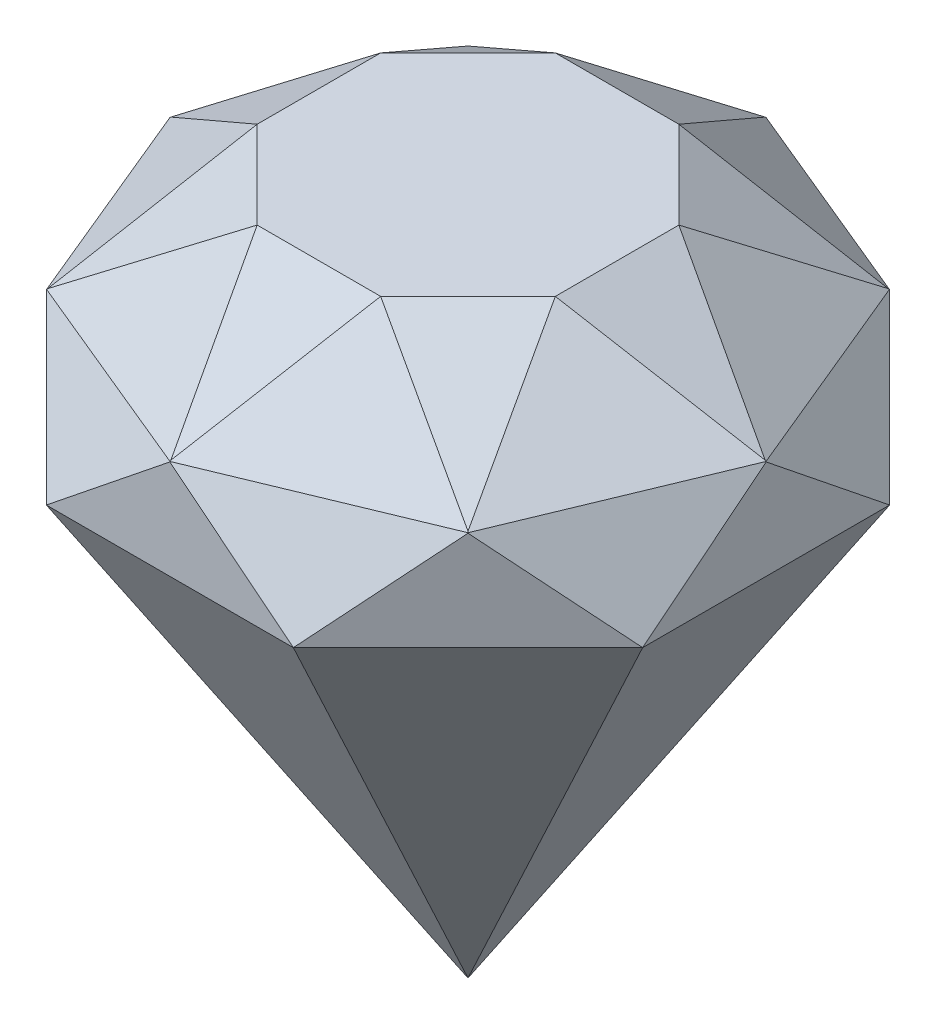
SolidWorks part; units mm, degrees
ref_plane "Front Plane" through (0, 0, 0) normal (0, 0, 1) x (1, 0, 0)
ref_plane "Top Plane" through (0, 0, 0) normal (0, 1, 0) x (1, 0, 0)
ref_plane "Right Plane" through (0, 0, 0) normal (1, 0, 0) x (0, 0, -1)
sketch "Sketch1" plane through (0, 0, 0) normal (0, 1, 0) x (1, 0, 0)
  line L0 (0, 0) -> (-12.4264, 30)
  line L1 (0, 0) -> (12.4264, 30)
  line L2 (12.4264, 30) -> (-12.4264, 30)
  line L3 (0, 0) -> (0, 30) construction
  dimension "D1" = 45
  dimension "D2" = 30
extrude "Boss-Extrude1" add sketch "Sketch1" along normal blind 70
sketch "Sketch2" plane through (0, 0, 0) normal (1, 0, 0) x (0, 0, -1)
  line L0 (15, 70) -> (30, 60)
  line L1 (0, 70) -> (30, 70) construction
  line L2 (30, 70) -> (30, 0) construction
  line L3 (30, 70) -> (30, 60)
  line L4 (30, 50) -> (0, 0)
  line L5 (0, 0) -> (30, 0)
  line L6 (30, 50) -> (30, 0)
  line L7 (30, 70) -> (15, 70)
  dimension "D1" = 15
  dimension "D2" = 10
  dimension "D3" = 10
extrude "Cut-Extrude1" cut sketch "Sketch2" against normal through all both and the other way through all
ref_axis "Axis1" through (0, -3.5, 0) along (0, 1, 0)
pattern_circular "CirPattern1" count 8 every 45 about axis through (0, -3.5, 0) along (0, 1, 0) of "Boss-Extrude1", "Cut-Extrude1"
ref_plane "Plane1" through (0, 0, 0) normal (0.9239, 0, -0.3827) x (0, 1, 0)
sketch "Sketch3" plane through (0, 0, 0) normal (0.9239, 0, -0.3827) x (0, 1, 0)
  line L4 (70, 32.4718) -> (70, 16.2359)
  line L9 (70, 16.2359) -> (60, 27.7)
  line L10 (60, 27.7) -> (50, 32.4718)
  line L11 (50, 32.4718) -> (70, 32.4718)
  line L12 (70, 11.4805) -> (70, 16.2359) construction
  line L13 (60, 32.4718) -> (50, 32.4718) construction
  line L15 (-3.5, 0) -> (73.5, 0) construction
  point P9 (0, 0)
  point P10 (60, 28.9787)
  point P12 (0, 0)
  dimension "D1" = 27.7
  dimension "D2" = 10
extrude "Cut-Extrude2" cut sketch "Sketch3" against normal through all both and the other way through all contours L4 region at (10.5134, 64.1987, 25.3815)
pattern_circular "CirPattern2" count 8 every 45 about axis through (0, -3.5, 0) along (0, 1, 0) of "Cut-Extrude2"
